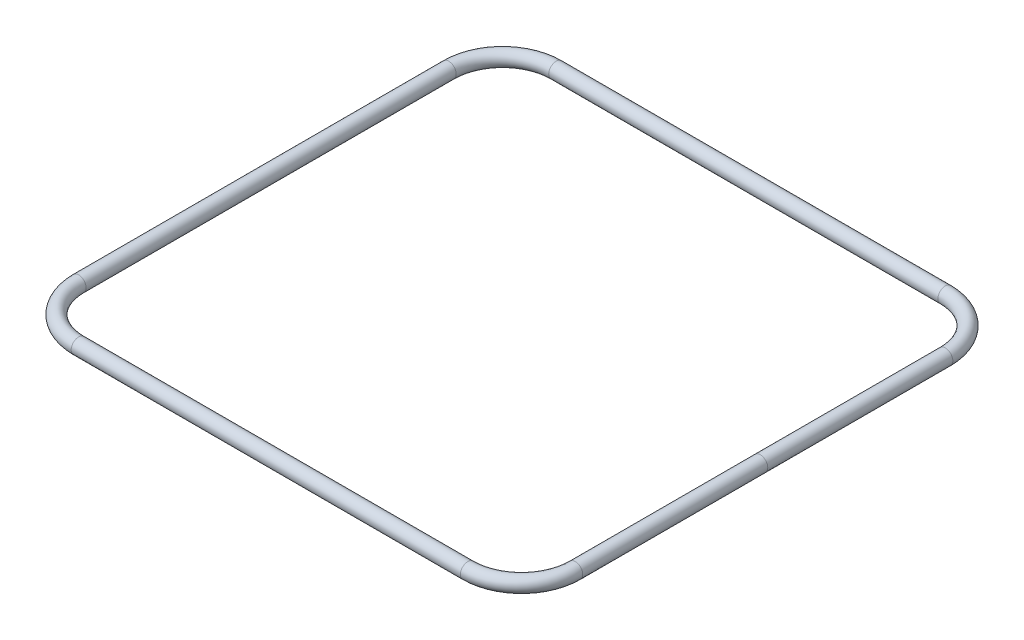
SolidWorks part; units mm, degrees
ref_plane "Front Plane" through (0, 0, 0) normal (0, 0, 1) x (1, 0, 0)
ref_plane "Top Plane" through (0, 0, 0) normal (0, 1, 0) x (1, 0, 0)
ref_plane "Right Plane" through (0, 0, 0) normal (1, 0, 0) x (0, 0, -1)
sketch "BaseDimensions" plane through (0, 0, 0) normal (0, 1, 0) x (1, 0, 0)
  line L0 (0, -63.5) -> (0, 63.5) construction
  line L1 (63.5, 0) -> (-63.5, 0) construction
  point P5 (0, 0)
  point P6 (0, 0)
  dimension "D1" = 127
  dimension "D2" = 127
sketch "O-RingPath" plane through (0, 0, 0) normal (0, 1, 0) x (1, 0, 0)
  line L0 (45.9922, -56.4388) -> (-45.9922, -56.4388)
  line L1 (58.6922, -43.7388) -> (58.6922, 43.7388)
  line L2 (0, 0) -> (0, -56.4388) construction
  line L3 (58.6922, 0) -> (0, 0) construction
  line L4 (-58.6922, -43.7388) -> (-58.6922, 43.7388)
  line L5 (45.9922, 56.4388) -> (-45.9922, 56.4388)
  arc A0 (45.9922, -56.4388) -> (58.6922, -43.7388) centre (45.9922, -43.7388) ccw
  arc A1 (-45.9922, -56.4388) -> (-58.6922, -43.7388) centre (-45.9922, -43.7388) cw
  arc A2 (-45.9922, 56.4388) -> (-58.6922, 43.7388) centre (-45.9922, 43.7388) ccw
  arc A3 (45.9922, 56.4388) -> (58.6922, 43.7388) centre (45.9922, 43.7388) cw
  point P17 (-58.6922, 0)
  dimension "D2" = 12.7
  dimension "D3" = 7.0612
sketch "O-RingProfile" plane through (0, 0, 0) normal (0, 0, 1) x (1, 0, 0)
  circle A0 centre (58.6922, 0) radius 1.7653
  dimension "D1" = 3.5306
sweep "Sweep2" add profiles "O-RingProfile" path "O-RingPath"
ref_plane "TopOfRing" through (0, 1.7653, 0) normal (0, 1, 0) x (1, 0, 0)
ref_plane "BottomOfRing" through (0, -1.7653, 0) normal (0, -1, 0) x (-1, 0, 0)
equation "\"D1@O-RingProfile\" = \"O-Ring_CS@BladderAssembly.Assembly\""
equation "\"D1@BaseDimensions\"=\"BaseWidth@BladderAssembly.Assembly\""
equation "\"D2@BaseDimensions\"=\"BaseLength@BladderAssembly.Assembly\""
equation "\"O_Ring_Len\"= \"O-Ring_Len@BladderAssembly.Assembly\""
equation "\"D1@O-RingPath\"=\"O_Ring_Len\""
